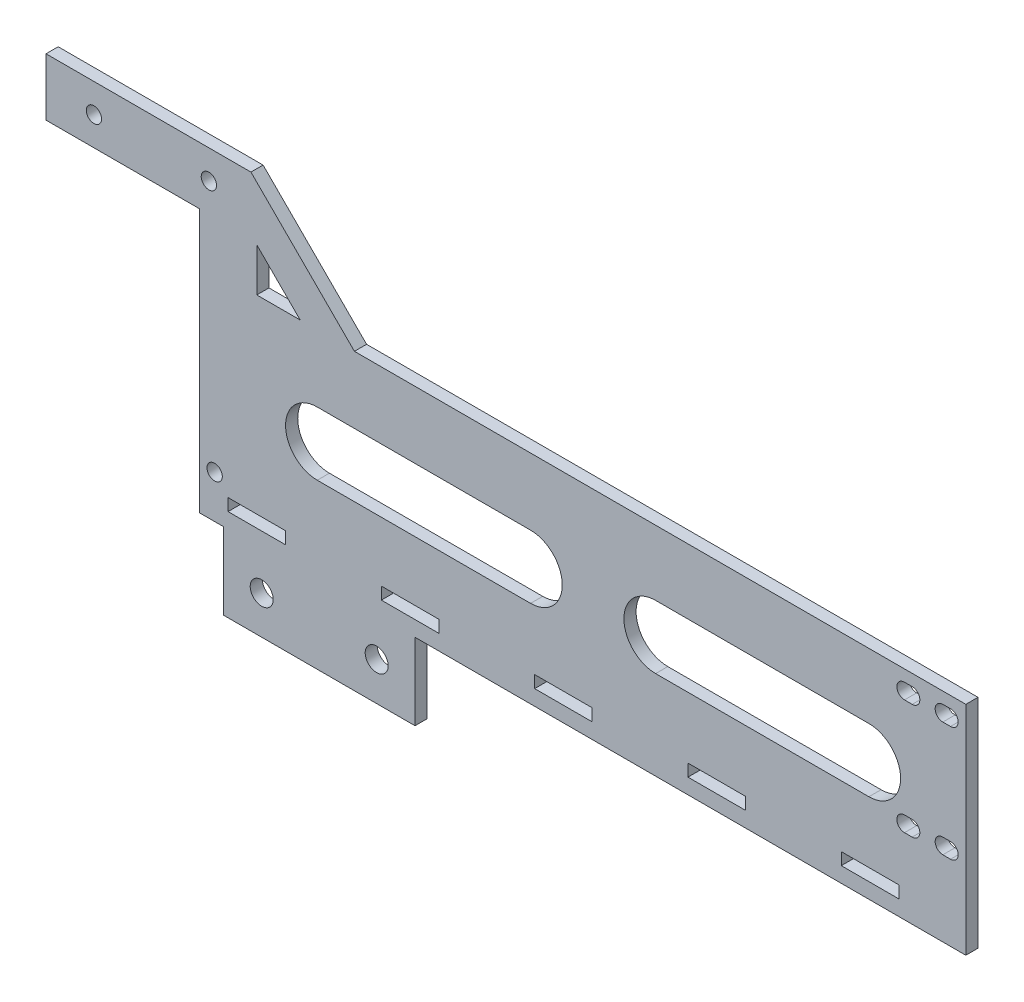
SolidWorks part; units mm, degrees
material "1060 Alloy"
ref_plane "Front Plane" through (0, 0, 0) normal (0, 0, 1) x (1, 0, 0)
ref_plane "Top Plane" through (0, 0, 0) normal (0, 1, 0) x (1, 0, 0)
ref_plane "Right Plane" through (0, 0, 0) normal (1, 0, 0) x (0, 0, -1)
sketch "Sketch1" plane through (0, 0, 0) normal (0, 0, 1) x (1, 0, 0)
  line L1 (-1.53, -68.5) -> (25.47, -95.5)
  line L2 (25.47, -95.5) -> (185, -95.5)
  line L5 (185, -95.5) -> (185, -143.5)
  line L6 (167.5, -145.03) -> (152.5, -145.03)
  line L7 (32.5, -145.03) -> (32.5, -148.205)
  line L9 (7.5, -148.205) -> (7.5, -145.03)
  line L12 (-55, -68.5) -> (-55, -83.5)
  line L13 (-55, -83.5) -> (-15, -83.5)
  line L15 (-7.5, -145.03) -> (7.5, -145.03)
  line L16 (0, -84.1721) -> (11.3279, -95.5)
  line L17 (11.3279, -95.5) -> (0, -95.5)
  line L18 (0, -95.5) -> (0, -84.1721)
  line L22 (72.5, -145.03) -> (72.5, -148.205)
  line L24 (47.5, -148.205) -> (47.5, -145.03)
  line L25 (112.5, -145.03) -> (112.5, -148.205)
  line L27 (87.5, -148.205) -> (87.5, -145.03)
  line L28 (152.5, -145.03) -> (152.5, -148.205)
  line L30 (127.5, -148.205) -> (127.5, -145.03)
  line L31 (47.5, -145.03) -> (32.5, -145.03)
  line L32 (87.5, -145.03) -> (72.5, -145.03)
  line L33 (127.5, -145.03) -> (112.5, -145.03)
  line L36 (-7.5, -148.205) -> (-7.5, -145.03)
  line L37 (-7.5, -148.205) -> (7.5, -148.205) construction
  line L38 (-55, -68.5) -> (-1.53, -68.5)
  line L41 (104.0581, -120.7579) -> (159.7098, -120.7579) construction
  line L42 (104.0581, -112.4884) -> (159.7098, -112.4884)
  line L43 (104.0581, -129.0275) -> (159.7098, -129.0275)
  line L44 (15.7752, -121.2049) -> (71.427, -121.2049) construction
  line L45 (15.7752, -112.9354) -> (71.427, -112.9354)
  line L46 (15.7752, -129.4745) -> (71.427, -129.4745)
  line L47 (-15, -150.03) -> (-15, -83.5)
  line L48 (190.8745, -115.5) -> (169.5, -115.5) construction
  line L49 (185, -95.25) -> (185, -135.25) construction
  line L50 (181, -100.5) -> (179, -100.5) construction
  line L51 (181, -102.5) -> (179, -102.5)
  line L52 (181, -98.5) -> (179, -98.5)
  line L53 (171, -100.5) -> (169, -100.5) construction
  line L54 (171, -102.5) -> (169, -102.5)
  line L55 (171, -98.5) -> (169, -98.5)
  line L56 (185, -143.5) -> (185, -148.5)
  line L57 (-7.5, -148.205) -> (7.5, -148.205)
  line L58 (-15, -150.03) -> (-15, -152.205)
  line L59 (-15, -152.205) -> (-8.7185, -152.205)
  line L60 (185, -148.5) -> (185, -152.205)
  line L61 (167.5, -145.03) -> (167.5, -148.205)
  line L62 (32.5, -148.205) -> (47.5, -148.205)
  line L63 (72.5, -148.205) -> (87.5, -148.205)
  line L64 (152.5, -148.205) -> (167.5, -148.205)
  line L65 (112.5, -148.205) -> (127.5, -148.205)
  line L66 (171, -130.5) -> (169, -130.5) construction
  line L67 (171, -128.5) -> (169, -128.5)
  line L68 (171, -132.5) -> (169, -132.5)
  line L69 (181, -130.5) -> (179, -130.5) construction
  line L70 (181, -128.5) -> (179, -128.5)
  line L71 (181, -132.5) -> (179, -132.5)
  line L72 (16.2815, 4.6252) -> (16.2815, -181.5625) construction
  line L74 (-8.7185, -152.205) -> (-8.7185, -172.205)
  line L75 (-8.7185, -172.205) -> (41.2815, -172.205)
  line L76 (41.2815, -152.205) -> (41.2815, -172.205)
  line L77 (1.2815, -162.205) -> (31.2815, -162.205) construction
  line L78 (-42.5, -76) -> (-12.5, -76) construction
  line L79 (41.2815, -152.205) -> (185, -152.205)
  arc A5 (104.0581, -112.4884) -> (104.0581, -129.0275) centre (104.0581, -120.7579) ccw
  arc A6 (159.7098, -129.0275) -> (159.7098, -112.4884) centre (159.7098, -120.7579) ccw
  arc A7 (15.7752, -112.9354) -> (15.7752, -129.4745) centre (15.7752, -121.2049) ccw
  arc A8 (71.427, -129.4745) -> (71.427, -112.9354) centre (71.427, -121.2049) ccw
  arc A9 (181, -102.5) -> (181, -98.5) centre (181, -100.5) ccw
  arc A10 (179, -98.5) -> (179, -102.5) centre (179, -100.5) ccw
  arc A11 (171, -102.5) -> (171, -98.5) centre (171, -100.5) ccw
  arc A12 (169, -98.5) -> (169, -102.5) centre (169, -100.5) ccw
  arc A13 (171, -128.5) -> (171, -132.5) centre (171, -130.5) cw
  arc A14 (169, -132.5) -> (169, -128.5) centre (169, -130.5) cw
  arc A15 (181, -128.5) -> (181, -132.5) centre (181, -130.5) cw
  arc A16 (179, -132.5) -> (179, -128.5) centre (179, -130.5) cw
  circle A17 centre (1.2815, -162.205) radius 3
  circle A18 centre (31.2815, -162.205) radius 3
  circle A19 centre (-42.5, -76) radius 2
  circle A20 centre (-12.5, -76) radius 2
  circle A21 centre (-11, -141.03) radius 2
  point P13 (180, -100.5)
  point P26 (170, -100.5)
  point P45 (40, -145.03)
  point P54 (131.884, -120.7579)
  point P61 (43.6011, -121.2049)
  point P69 (170, -130.5)
  point P76 (180, -130.5)
  point P89 (16.2815, -172.205)
  point P94 (41.2815, -162.205)
  point P95 (16.2815, -162.205)
  point P99 (-55, -76)
  dimension "D8" = 2
  dimension "D25" = 6
  dimension "D10" = 4
  dimension "D30" = 4
  dimension "40" = 40
  dimension "D3" = 5
  dimension "D4" = 10
  dimension "D5" = 15
  dimension "D6" = 4
  dimension "D7" = 4
  dimension "D9" = 10
  dimension "D11" = 12
  dimension "D12" = 4
  dimension "D13" = 7.5
  dimension "D14" = 15
  dimension "D15" = 25
  dimension "D16" = 3.175
  dimension "D17" = 15
  dimension "D19" = 15
  dimension "D20" = 61.53
  dimension "D21" = 200
  dimension "D22" = 50
  dimension "D23" = 20
  dimension "D24" = 30
  dimension "D26" = 30
  dimension "D27" = 12.5
  dimension "D28" = 4
  dimension "D29" = 4
  dimension "D18" = 4
base flange "Base-Flange1" sketch "Sketch1" thickness 3.175 reverse thickness direction no parameters "D1"=0.7366
sketch "Bend-Lines1" [suppressed] plane through (0, 0, 0) normal (0, 1, 0) x (1, 0, 0)
sketch "Bounding-Box1" [suppressed] plane through (0, 0, 0) normal (0, 1, 0) x (1, 0, 0)
sheet metal parameters "Sheet-Metal1" thickness 3.175 parameters "D1"=0.7366
flat pattern "Flat-Pattern1" [suppressed]
sketch "Bend-Lines2" plane through (0, 0, 0) normal (0, 1, 0) x (1, 0, 0)
sketch3d "Bounding-Box2" [suppressed]
  line L0 (-55, -172.205, 0) -> (185, -172.205, 0) construction
  line L1 (-55, -68.5, 0) -> (185, -68.5, 0) construction
  line L2 (-55, -172.205, 0) -> (-55, -68.5, 0) construction
  line L3 (185, -172.205, 0) -> (185, -68.5, 0) construction
